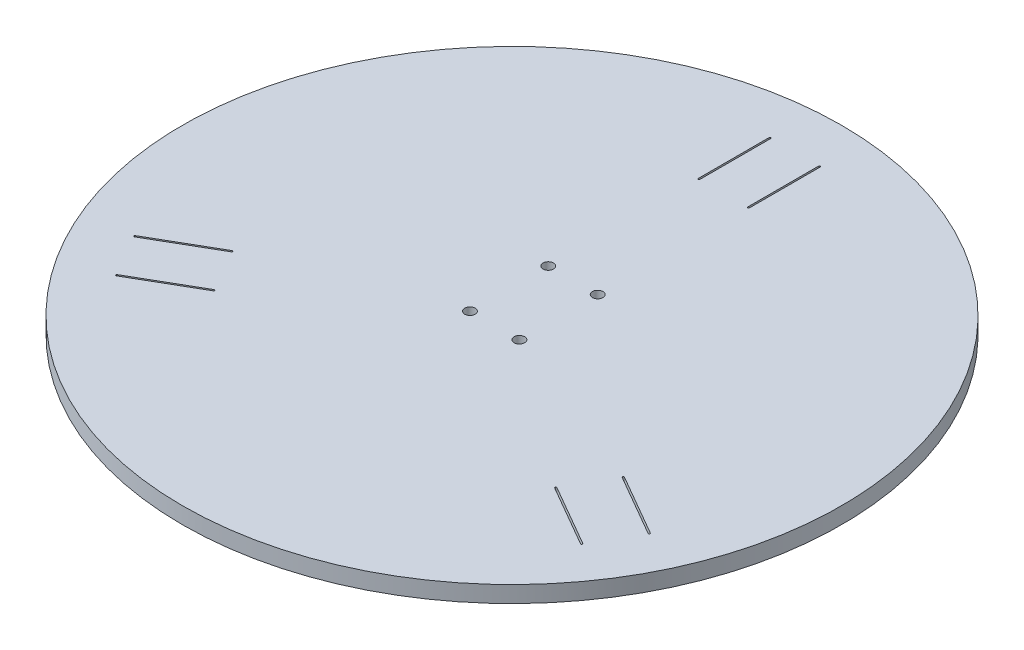
SolidWorks part; units mm, degrees
ref_plane "Front Plane" through (0, 0, 0) normal (0, 0, 1) x (1, 0, 0)
ref_plane "Top Plane" through (0, 0, 0) normal (0, 1, 0) x (1, 0, 0)
ref_plane "Right Plane" through (0, 0, 0) normal (1, 0, 0) x (0, 0, -1)
sketch "Sketch2" plane through (0, 0, 0) normal (0, 1, 0) x (1, 0, 0)
  circle A0 centre (0, 0) radius 100
  dimension "D1" = 200
extrude "Boss-Extrude1" add sketch "Sketch2" along normal blind 5
sketch "Sketch3" plane through (0, 5, 0) normal (0, 1, 0) x (1, 0, 0)
  line L0 (0, 0) -> (0, 100) construction
  line L1 (-7.5, 75) -> (7.5, 75) construction
  line L3 (-7.75, 64) -> (-7.25, 64)
  line L4 (-7.75, 64) -> (-7.75, 86)
  line L5 (-7.75, 86) -> (-7.25, 86)
  line L6 (-7.25, 64) -> (-7.25, 86)
  line L7 (-7.75, 64) -> (-7.25, 86) construction
  line L8 (-7.75, 86) -> (-7.25, 64) construction
  line L9 (7.25, 64) -> (7.75, 64)
  line L10 (7.25, 64) -> (7.25, 86)
  line L11 (7.25, 86) -> (7.75, 86)
  line L12 (7.75, 64) -> (7.75, 86)
  line L13 (7.25, 64) -> (7.75, 86) construction
  line L14 (7.25, 86) -> (7.75, 64) construction
  line L30 (59.3006, -25.2883) -> (78.3532, -36.2883)
  line L31 (59.3006, -25.2883) -> (59.0506, -25.7213)
  line L32 (59.0506, -25.7213) -> (78.1032, -36.7213)
  line L33 (78.3532, -36.2883) -> (78.1032, -36.7213)
  line L34 (51.8006, -38.2787) -> (70.8532, -49.2787)
  line L35 (51.8006, -38.2787) -> (51.5506, -38.7117)
  line L36 (51.5506, -38.7117) -> (70.6032, -49.7117)
  line L37 (70.8532, -49.2787) -> (70.6032, -49.7117)
  line L38 (-51.5506, -38.7117) -> (-70.6032, -49.7117)
  line L39 (-51.5506, -38.7117) -> (-51.8006, -38.2787)
  line L40 (-51.8006, -38.2787) -> (-70.8532, -49.2787)
  line L41 (-70.6032, -49.7117) -> (-70.8532, -49.2787)
  line L42 (-59.0506, -25.7213) -> (-78.1032, -36.7213)
  line L43 (-59.0506, -25.7213) -> (-59.3006, -25.2883)
  line L44 (-59.3006, -25.2883) -> (-78.3532, -36.2883)
  line L45 (-78.1032, -36.7213) -> (-78.3532, -36.2883)
  circle A0 centre (0, 0) radius 100 construction
  point P8 (0, 75)
  point P34 (0, 0)
  point P36 (0, 0)
  dimension "D1" = 15
  dimension "D2" = 22
  dimension "D3" = 0.5
  dimension "D4" = 75
  dimension "D5" = 3
extrude "Cut-Extrude1" cut sketch "Sketch3" against normal through all
sketch "Sketch6" plane through (0, 0, 0) normal (0, -1, 0) x (-1, 0, 0)
  line L0 (0, 0) -> (0, 50000) construction
  line L1 (0, 0) -> (50000, 0) construction
  point P0 (-7.5, 18.5)
  point P2 (7.5, 18.5)
  point P4 (7.5, -5.25)
  point P6 (-7.5, -5.25)
  dimension "D1" = 15
  dimension "D2" = 18.5
  dimension "D3" = 23.75
hole_wizard "Ø3.2 (3.2) Diameter Hole1" positions "Sketch6" profile "Sketch5" hole size "Ø3.2" standard "ANSI Metric" end condition through all
sketch "Sketch5" plane through (7.5, 0, -18.5) normal (1, 0, 0) x (0, 0, -1)
  line L0 (0, 0) -> (0, 5)
  line L1 (0, 5) -> (1.6, 5)
  line L2 (1.6, 5) -> (1.6, 0.025)
  line L3 (1.6, 0.025) -> (1.625, 0)
  line L5 (1.625, 0) -> (0, 0)
  line L6 (-1.6, 0.025) -> (-1.625, 0) construction
  line L11 (0, -6.35) -> (0, 107.95) construction
  dimension "Thru Hole Dia." = 3.2
  dimension "Thru Hole Depth" = 5
  dimension "Near C'Sink Dia." = 3.25
  dimension "Near C'Sink Angle" = 90
fillet "Fillet1" radius 0.2 24 edges at (59.0506, 2.5, 25.7213) (59.3006, 2.5, 25.2883) (78.3532, 2.5, 36.2883) (78.1032, 2.5, 36.7213) (-59.3006, 2.5, 25.2883) (-59.0506, 2.5, 25.7213) (-78.1032, 2.5, 36.7213) (-78.3532, 2.5, 36.2883) (-51.8006, 2.5, 38.2787) (-51.5506, 2.5, 38.7117) (-70.6032, 2.5, 49.7117) (-70.8532, 2.5, 49.2787) (51.5506, 2.5, 38.7117) (51.8006, 2.5, 38.2787) (70.8532, 2.5, 49.2787) (70.6032, 2.5, 49.7117) (7.25, 2.5, -64) (7.25, 2.5, -86) (7.75, 2.5, -86) (7.75, 2.5, -64) (-7.75, 2.5, -64) (-7.25, 2.5, -86) (-7.25, 2.5, -64) (-7.75, 2.5, -86)
equation "\"Leg_Spacing\"=40"
equation "\"Leaf_Spring_Slot_Width\"=5"
equation "\"Leaf_Spring_Thickness\"=0.2"
equation "\"Inner_Radius\"=75"
equation "\"Camera\"=120"
